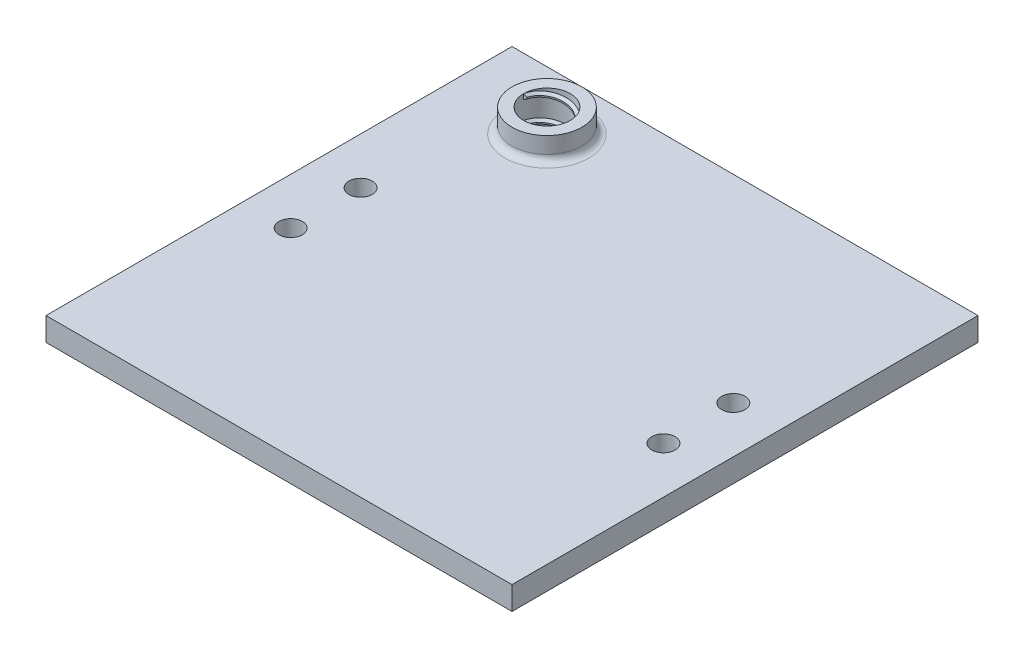
SolidWorks part; units mm, degrees
ref_plane "Front Plane" through (0, 0, 0) normal (0, 0, 1) x (1, 0, 0)
ref_plane "Top Plane" through (0, 0, 0) normal (0, 1, 0) x (1, 0, 0)
ref_plane "Right Plane" through (0, 0, 0) normal (1, 0, 0) x (0, 0, -1)
sketch "Sketch1" plane through (0, 0, 0) normal (0, 1, 0) x (1, 0, 0)
  line L1 (-100, 100) -> (100, 100)
  line L2 (-100, 100) -> (-100, -100)
  line L3 (-100, -100) -> (100, -100)
  line L4 (100, 100) -> (100, -100)
  line L5 (-100, 100) -> (100, -100) construction
  line L6 (-100, -100) -> (100, 100) construction
  point P0 (0, 0)
  dimension "D1" = 200
  dimension "D2" = 200
extrude "Boss-Extrude1" add sketch "Sketch1" along normal blind 10
sketch "Sketch2" plane through (0, 0, 0) normal (0, 1, 0) x (1, 0, 0)
  line L0 (-100, 100) -> (-100, -100) construction
  line L1 (100, -100) -> (100, 100) construction
  line L2 (-100, -100) -> (100, -100) construction
  circle A0 centre (-80, 15) radius 5
  circle A1 centre (-80, -15) radius 5
  circle A2 centre (80, 15) radius 5
  circle A3 centre (80, -15) radius 5
  dimension "D1" = 10
  dimension "D2" = 10
  dimension "D3" = 10
  dimension "D4" = 10
  dimension "D5" = 20
  dimension "D6" = 20
  dimension "D7" = 20
  dimension "D8" = 20
  dimension "D9" = 30
  dimension "D10" = 30
  dimension "D11" = 85
  dimension "D12" = 85
extrude "Cut-Extrude1" cut sketch "Sketch2" along normal through all both
sketch "Sketch3" plane through (0, 0, 0) normal (0, 1, 0) x (1, 0, 0)
  line L0 (-100, 100) -> (-100, -100) construction
  line L1 (100, 100) -> (-100, 100) construction
  circle A0 centre (-60, 75) radius 10
  circle A1 centre (-60, 75) radius 15
  dimension "D1" = 20
  dimension "D2" = 30
  dimension "D3" = 40
  dimension "D4" = 25
extrude "Boss-Extrude2" add sketch "Sketch3" along normal blind 20 and the other way blind 10
fillet "Fillet1" radius 3 2 edges at (-60, 0, -60) (-60, 10, -60)
sketch "Sketch8" plane through (0, 0, 0) normal (0, 1, 0) x (1, 0, 0)
  line L0 (-100, 100) -> (-100, -100) construction
  line L1 (100, 100) -> (-100, 100) construction
  circle A0 centre (-60, 75) radius 10
  dimension "D1" = 20
  dimension "D2" = 40
  dimension "D3" = 25
extrude "Cut-Extrude2" cut sketch "Sketch8" against normal through all both and the other way through all
thread "Thread1" pitch 2.5 method extrude profile "Thread Profile1" start angle 0, offset 0, length 30, pitch 10, diameter 20
ref_plane "Plane1" through (-70, 20, -75) normal (0, 0, 1) x (-1, 0, 0)
sketch "Thread Profile1" plane through (-70, 20, -75) normal (0, 0, 1) x (-1, 0, 0)
  line L0 (0, 0) -> (0, 2.5) construction
  line L11 (0, 0) -> (0, 2.1875)
  line L12 (0, 2.1875) -> (-1.3532, 1.4062)
  line L13 (-1.3532, 1.4062) -> (-1.3532, 0.7812)
  line L15 (-1.3532, 0.7812) -> (0, 0)
  line L17 (-1.3532, 1.0937) -> (0, 1.0937) construction
  point P2 (0, 0)
  dimension "Pitch" = 2.5
  dimension "Profile_Angle" = 60
  dimension "Profile_Land" = 0.625
  dimension "Profile_Height" = 1.3532
sketch "Sketch11" plane through (0, 0, 0) normal (0, 0, 1) x (1, 0, 0)
  line L0 (-75, -10) -> (-45, -10)
  line L1 (-45, -10) -> (-45, -15.9726)
  line L2 (-45, -15.9726) -> (-75, -15.9726)
  line L3 (-75, -15.9726) -> (-75, -10)
extrude "Cut-Extrude3" cut sketch "Sketch11" against normal through all both
